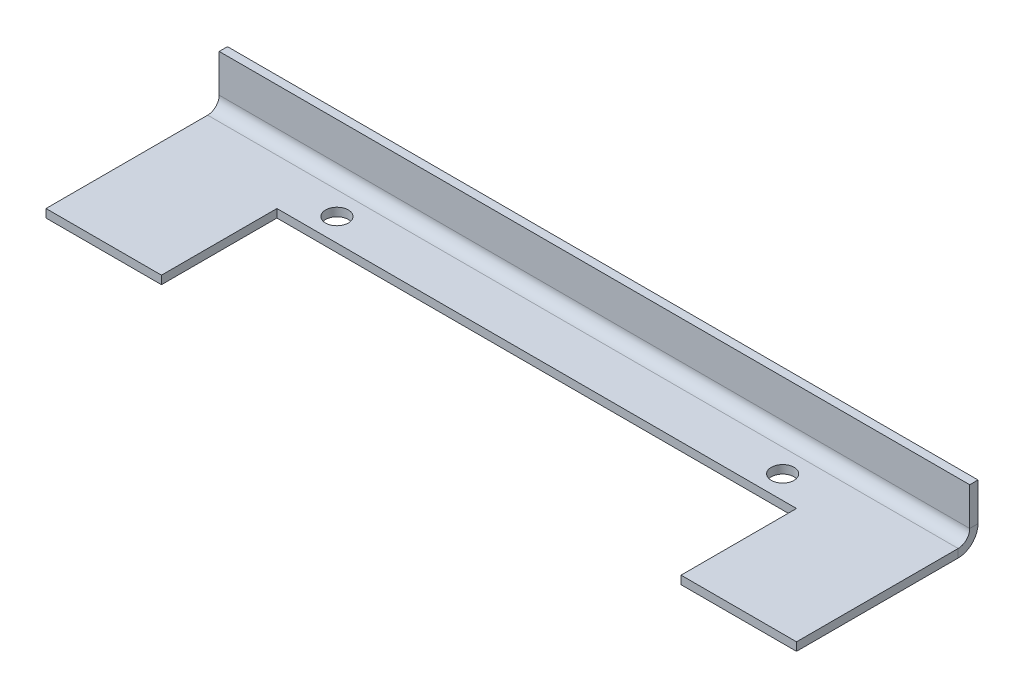
SolidWorks part; units mm, degrees
note: The reader was unsure of these and kept them because the rebuilt part matched: flange length of "Edge-Flange1".
material "1060 Alloy"
ref_plane "Front" through (0, 0, 0) normal (0, 0, 1) x (1, 0, 0)
ref_plane "Top" through (0, 0, 0) normal (0, 1, 0) x (1, 0, 0)
ref_plane "Right" through (0, 0, 0) normal (1, 0, 0) x (0, 0, -1)
sketch "Sketch1" plane through (0, 0, 0) normal (0, 1, 0) x (1, 0, 0)
  line L0 (0, 0) -> (0, -19.05)
  line L1 (12.7, -6.35) -> (69.85, -6.35)
  line L3 (0, 0) -> (82.55, 0)
  line L6 (82.55, 0) -> (82.55, -19.05)
  line L7 (82.55, -19.05) -> (69.85, -19.05)
  line L8 (69.85, -6.35) -> (69.85, -19.05)
  line L11 (0, -19.05) -> (12.7, -19.05)
  line L12 (12.7, -6.35) -> (12.7, -19.05)
  dimension "D1" = 82.55
  dimension "D2" = 6.35
  dimension "D3" = 12.7
  dimension "D4" = 12.7
base flange "Base-Flange1" sketch "Sketch1" thickness 0.9119 reverse thickness direction no parameters "D1"=1.27
hole_wizard "Ø2.5mm Dowel Hole1" positions "Sketch10" profile "Sketch11" hole size "Ø2.5" standard "ANSI Metric" end condition up to next
sketch "Sketch10" plane through (0, -0.9119, 0) normal (0, -1, 0) x (-1, 0, 0)
  line L0 (-12.7, -6.35) -> (-69.85, -6.35) construction
  line L1 (-65.786, -3.81) -> (-16.764, -3.81) construction
  line L3 (-41.275, -6.35) -> (-41.275, 0) construction
  line L4 (-82.55, 0) -> (0, 0) construction
  point P0 (-65.786, -3.81)
  point P2 (-16.764, -3.81)
  point P23 (-41.275, -3.81)
  dimension "D1" = 2.54
  dimension "D2" = 49.022
sketch "Sketch11" plane through (65.786, -0.9119, 3.81) normal (1, 0, 0) x (0, 0, -1)
  line L0 (0, 0) -> (0, 0.9119)
  line L1 (0, 0.9119) -> (1.25, 0.9119)
  line L2 (1.25, 0.9119) -> (1.25, 0)
  line L5 (1.25, 0) -> (0, 0)
  line L11 (0, -6.35) -> (0, 107.95) construction
  dimension "Thru Hole Dia." = 2.5
  dimension "Thru Hole Depth" = 0.9119
edge flange "Edge-Flange1" sketch "Sketch14" flange angle 90 flange length 6.35 flange position material outside bend radius 1.27 thickness 0.9119 relief rectangular parameters "D6"=10
sketch "Sketch14" plane through (0, 0, 0) normal (0, 0, -1) x (-1, 0, 0)
  line L2 (-82.55, 0) -> (-82.55, 5.4381)
  line L3 (-82.55, 5.4381) -> (0, 5.4381)
  line L4 (0, 5.4381) -> (0, 0)
  line L5 (-82.55, 0) -> (0, 0) construction
  line L6 (-82.55, 0) -> (0, 0)
bend "EdgeBend1" bend radius 1.27 bend angle 90 parameters "D5"=1
sketch "Bend-Lines1" [suppressed] plane through (0, 0, 0) normal (0, 1, 0) x (1, 0, 0)
sketch "Bounding-Box1" [suppressed] plane through (0, 0, 0) normal (0, 1, 0) x (1, 0, 0)
sheet metal parameters "Sheet-Metal1" thickness 0.9119 parameters "D1"=1.27
flat pattern "Flat-Pattern1" [suppressed]
sketch "Bend-Lines2" plane through (0, 0, 0) normal (0, 1, 0) x (1, 0, 0)
  line L0 (0, 6.7803) -> (82.55, 6.7803) construction
  line L1 (0, 6.7803) -> (82.55, 6.7803) construction
sketch3d "Bounding-Box2" [suppressed]
  line L0 (82.55, 19.05, 0) -> (0, 19.05, 0) construction
  line L1 (82.55, 0, 0) -> (0, 0, 0) construction
  line L2 (82.55, 19.05, 0) -> (82.55, 0, 0) construction
  line L3 (0, 19.05, 0) -> (0, 0, 0) construction
sheet metal parameters "Sheet-Metal2" thickness 0.9119 parameters "D1"=1.27
flat pattern "Flat-Pattern1"
sketch "Bend-Lines2" plane through (0, 0, 0) normal (0, 1, 0) x (1, 0, 0)
sketch3d "Bounding-Box2" [suppressed]
  line L0 (82.55, 0, 0) -> (0, 0, 0) construction
  line L1 (82.55, -19.05, 0) -> (0, -19.05, 0) construction
  line L2 (82.55, 0, 0) -> (82.55, -19.05, 0) construction
  line L3 (0, 0, 0) -> (0, -19.05, 0) construction
sheet metal parameters "Sheet-Metal3" thickness 0.9119 parameters "D1"=1.27
flat pattern "Flat-Pattern1"
sketch "Bend-Lines2" plane through (0, 0, 0) normal (0, 1, 0) x (1, 0, 0)
  line L0 (82.55, 0.0855) -> (0, 0.0855) construction
  line L1 (82.55, 0.0855) -> (0, 0.0855) construction
sketch3d "Bounding-Box2" [suppressed]
  line L0 (82.55, 5.6092, 0) -> (0, 5.6092, 0) construction
  line L1 (82.55, -12.7, 0) -> (0, -12.7, 0) construction
  line L2 (82.55, 5.6092, 0) -> (82.55, -12.7, 0) construction
  line L3 (0, 5.6092, 0) -> (0, -12.7, 0) construction
bend of the flat pattern "Flatten-<EdgeBend1>1"
